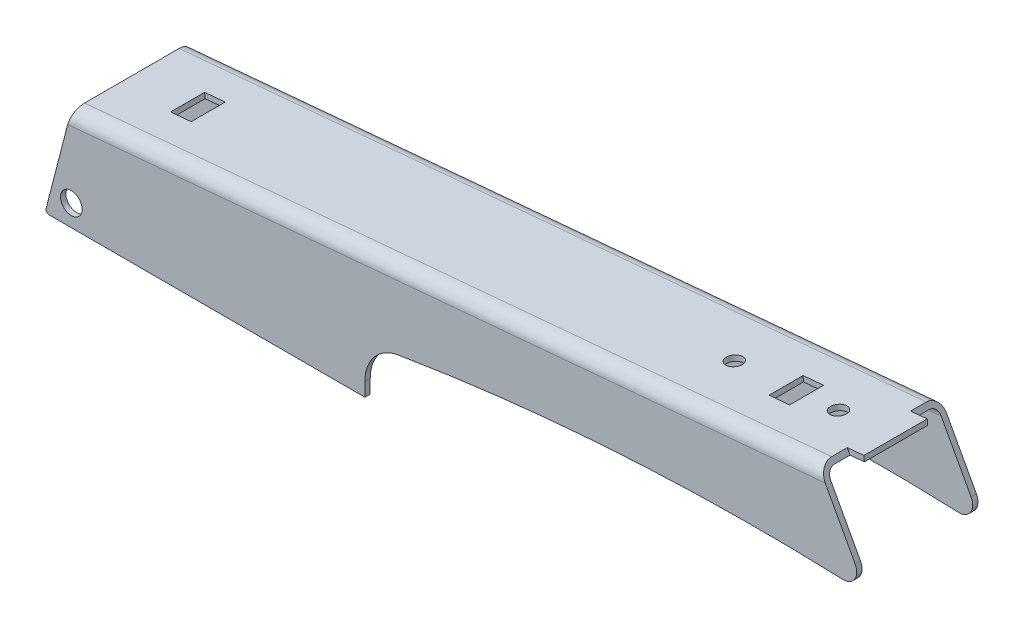
SolidWorks part; units mm, degrees
material "Chrome Stainless Steel"
ref_plane "Front Plane" through (0, 0, 0) normal (0, 0, 1) x (1, 0, 0)
ref_plane "Top Plane" through (0, 0, 0) normal (0, 1, 0) x (1, 0, 0)
ref_plane "Right Plane" through (0, 0, 0) normal (1, 0, 0) x (0, 0, -1)
ref_axis "X-axis" through (-88.99, 0, 0) along (1, 0, 0)
ref_axis "Y-axis" through (0, -55, 0) along (0, 1, 0)
ref_axis "Z-axis" through (0, 0, 55) along (0, 0, -1)
sketch "Sketch1" plane through (0, 0, 0) normal (0, 0, 1) x (1, 0, 0)
  line L0 (0, 0) -> (60.96, 0)
  line L1 (60.96, 0) -> (60.96, 2.6416)
  line L2 (154.3781, 19.2202) -> (147.3665, 32.131)
  line L3 (147.3665, 32.131) -> (4.9919, 19.304)
  line L4 (4.9919, 19.304) -> (0, 0)
  arc A0 (60.96, 2.6416) -> (67.3397, 10.16) centre (68.58, 2.6416) cw
  arc A1 (67.3397, 10.16) -> (152.0488, 15.4699) centre (135.9199, -405.5646) cw
  arc A2 (152.0488, 15.4699) -> (154.3781, 19.2202) centre (152.146, 18.008) ccw
  point P17 (109.5602, 14.9534)
  dimension "D7" = 7.62
  dimension "D8" = 2.54
  dimension "D1" = 154.686
  dimension "D2" = 60.96
  dimension "D3" = 19.304
  dimension "D4" = 19.939
  dimension "D5" = 10.16
  dimension "D6" = 17.4498
  dimension "D9" = 142.9512
  dimension "D10" = 32.131
  dimension "D11" = 13.716
extrude "Boss-Extrude1" add sketch "Sketch1" along normal mid plane 23.114
fillet "Fillet1" radius 2.54 2 edges at (76.1792, 25.7175, -11.557) (76.1792, 25.7175, 11.557)
fillet "Fillet2" radius 0.635 1 edges at (0, 0, 0)
shell "Shell1" thickness 1.016 removed face at (150.0527, 27.1848, 0) removed face at (153.7586, 17.0065, 0) removed face at (109.6272, 13.8841, 0) removed face at (60.96, 1.3208, 0) removed face at (63.4599, 6.9863, 0) removed face at (30.89, 0, 0) removed face at (0.4154, 0.3216, 0) removed face at (3.2179, 12.4439, 0)
ref_plane "Plane1" through (149.0514, 13.4285, 0) normal (0.996, 0.0897, 0) x (0, 0, -1)
sketch "Sketch3" plane through (149.0514, 13.4285, 0) normal (0.996, 0.0897, 0) x (0, 0, -1)
  line L0 (-9.017, 18.7782) -> (9.017, 18.7782) construction
  line L1 (-6.0325, 17.7622) -> (6.0325, 17.7622)
  line L2 (-6.0325, 17.7622) -> (-6.0325, 18.7782)
  line L3 (-6.0325, 18.7782) -> (6.0325, 18.7782)
  line L4 (6.0325, 17.7622) -> (6.0325, 18.7782)
  line L5 (-9.017, 17.7622) -> (9.017, 17.7622) construction
  point P8 (0, 17.7622)
  point P11 (0, 17.7622)
  dimension "D1" = 12.065
extrude "Boss-Extrude2" add sketch "Sketch3" along normal blind 3.175
sketch "Sketch4" plane through (-1.685, 18.7025, 0) normal (-0.0897, 0.996, 0) x (0.996, 0.0897, 0)
  line L0 (6.7039, -9.017) -> (6.7039, 9.017) construction
  line L1 (17.3719, -3.2385) -> (21.3089, -3.2385)
  line L2 (17.3719, -3.2385) -> (17.3719, 3.2385)
  line L3 (17.3719, 3.2385) -> (21.3089, 3.2385)
  line L4 (21.3089, -3.2385) -> (21.3089, 3.2385)
  line L5 (17.3719, -3.2385) -> (21.3089, 3.2385) construction
  line L6 (17.3719, 3.2385) -> (21.3089, -3.2385) construction
  line L7 (131.8751, -3.2385) -> (135.8121, -3.2385)
  line L8 (131.8751, -3.2385) -> (131.8751, 3.2385)
  line L9 (131.8751, 3.2385) -> (135.8121, 3.2385)
  line L10 (135.8121, -3.2385) -> (135.8121, 3.2385)
  line L11 (131.8751, -3.2385) -> (135.8121, 3.2385) construction
  line L12 (131.8751, 3.2385) -> (135.8121, -3.2385) construction
  line L13 (152.8301, 6.0325) -> (152.8301, -6.0325) construction
  line L14 (-16.639, 0) -> (191.4803, 0) construction
  circle A0 centre (121.9691, 0) radius 1.524
  circle A1 centre (141.9081, 0) radius 1.524
  point P0 (19.3404, 0)
  point P5 (133.8436, 0)
  dimension "D6" = 3.048
  dimension "D1" = 10.668
  dimension "D2" = 17.018
  dimension "D3" = 6.477
  dimension "D4" = 3.937
  dimension "D5" = 8.382
  dimension "D7" = 4.572
extrude "Cut-Extrude1" cut sketch "Sketch4" against normal through all
sketch "Sketch5" plane through (0, 0, 11.557) normal (0, 0, 1) x (1, 0, 0)
  line L0 (0.8201, 0) -> (60.96, 0) construction
  line L2 (4.3167, 16.6929) -> (0.2053, 0.794) construction
  circle A0 centre (5.0125, 4.064) radius 2.0574
  dimension "D2" = 4.1148
  dimension "D3" = 1.778
  dimension "D1" = 4.064
extrude "Cut-Extrude2" cut sketch "Sketch5" against normal through all
